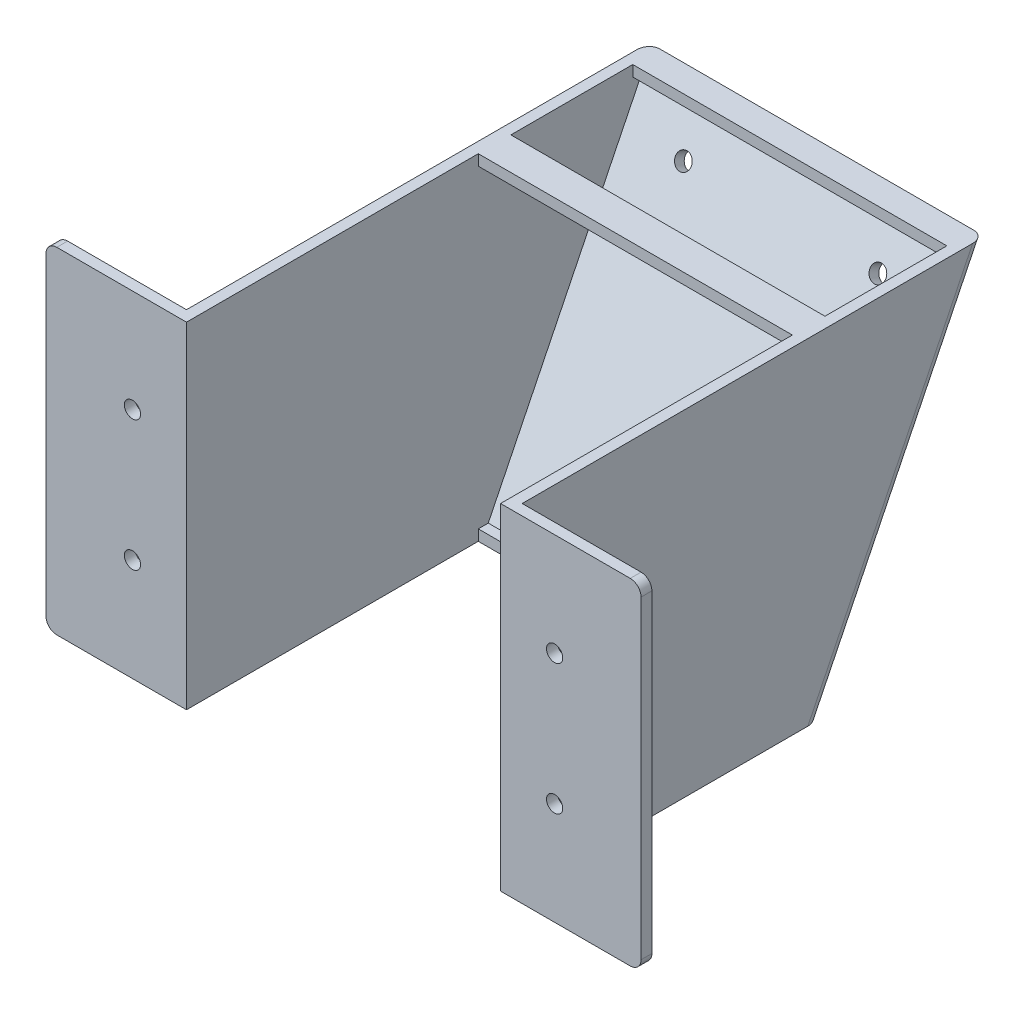
SolidWorks part; units mm, degrees
ref_plane "前视基准面" through (0, 0, 0) normal (0, 0, 1) x (1, 0, 0)
ref_plane "上视基准面" through (0, 0, 0) normal (0, 1, 0) x (1, 0, 0)
ref_plane "右视基准面" through (0, 0, 0) normal (1, 0, 0) x (0, 0, -1)
other "Configuration Table"
sketch "草图1" plane through (0, 0, 0) normal (0, 0, 1) x (1, 0, 0)
  line L5 (-31.0634, 31.0634) -> (31.0634, 31.0634)
  line L6 (-31.0634, 31.0634) -> (-31.0634, -31.0634)
  line L7 (-31.0634, -31.0634) -> (31.0634, -31.0634)
  line L8 (31.0634, 31.0634) -> (31.0634, -31.0634)
  line L9 (-31.0634, 31.0634) -> (31.0634, -31.0634) construction
  line L10 (-31.0634, -31.0634) -> (31.0634, 31.0634) construction
  point P0 (0, 0)
  point P1 (0, 0)
extrude "凸台-拉伸1" add sketch "草图1" along normal blind 57
sketch "草图3" plane through (0, 0, 57) normal (0, 0, 1) x (1, 0, 0)
  line L0 (-29.0634, 32.5965) -> (-29.0634, -33.672) construction
  line L1 (-31.0634, 31.0634) -> (-31.0634, -31.0634) construction
  line L2 (0, 32.5965) -> (0, -32.762) construction
  line L3 (29.0634, 32.5965) -> (29.0634, -33.672) construction
  line L4 (-29.0634, 31.0634) -> (29.0634, 31.0634)
  line L5 (31.0634, 31.0634) -> (-31.0634, 31.0634) construction
  line L6 (29.0634, 31.0634) -> (29.0634, -31.0634)
  line L7 (-31.0634, -31.0634) -> (31.0634, -31.0634) construction
  line L8 (29.0634, -31.0634) -> (-29.0634, -31.0634)
  line L9 (-29.0634, -31.0634) -> (-29.0634, 31.0634)
  dimension "D1" = 2
extrude "切除-拉伸5" cut sketch "草图3" against normal blind 54
sketch "草图4" plane through (31.0634, 0, 0) normal (1, 0, 0) x (0, 0, -1)
  line L0 (-55, 32.9321) -> (-55, -33.2279) construction
  line L1 (-57, -31.0634) -> (-57, 31.0634) construction
  line L2 (-57, 31.0634) -> (-55, 31.0634)
  line L3 (-57, 31.0634) -> (0, 31.0634) construction
  line L4 (-55, 31.0634) -> (-55, -31.0634)
  line L5 (-57, -31.0634) -> (0, -31.0634) construction
  line L6 (-55, -31.0634) -> (-57, -31.0634)
  line L7 (-57, -31.0634) -> (-57, 31.0634)
  dimension "D1" = 2
extrude "凸台-拉伸2" add sketch "草图4" along normal blind 24
sketch "草图5" plane through (-31.0634, 0, 0) normal (-1, 0, 0) x (0, 0, 1)
  line L0 (55, 32.4379) -> (55, -34.0321) construction
  line L1 (57, 31.0634) -> (57, -31.0634) construction
  line L2 (55, 31.0634) -> (57, 31.0634)
  line L3 (57, 31.0634) -> (0, 31.0634) construction
  line L4 (57, 31.0634) -> (57, -31.0634)
  line L5 (57, -31.0634) -> (55, -31.0634)
  line L6 (57, -31.0634) -> (0, -31.0634) construction
  line L7 (55, -31.0634) -> (55, 31.0634)
  dimension "D1" = 2
extrude "凸台-拉伸3" add sketch "草图5" along normal blind 24
sketch "草图6" plane through (0, 0, 57) normal (0, 0, 1) x (1, 0, 0)
  line L0 (39.0634, 37.283) -> (39.0634, -45.3289) construction
  line L1 (29.0634, -31.0634) -> (29.0634, 31.0634) construction
  line L2 (-58.8139, 12.0634) -> (65.5315, 12.0634) construction
  line L3 (55.0634, 31.0634) -> (29.0634, 31.0634) construction
  line L4 (0, 0) -> (0, -46.3341) construction
  line L5 (-12.2388, 0) -> (9.6324, 0) construction
  line L7 (-61.7606, -12.0634) -> (78.759, -12.0634) construction
  circle A0 centre (39.0634, 12.0634) radius 1.5
  circle A1 centre (-39.0634, 12.0634) radius 1.5
  circle A2 centre (39.0634, -12.0634) radius 1.5
  circle A3 centre (-39.0634, -12.0634) radius 1.5
  dimension "D1" = 10
  dimension "D2" = 19
extrude "切除-拉伸6" cut sketch "草图6" against normal blind 24
sketch "草图7" plane through (0, 0, 0) normal (0, 0, -1) x (-1, 0, 0)
  line L0 (0, 33.5434) -> (0, -41.5893) construction
  line L1 (-18, 33.5434) -> (-18, -43.8557) construction
  line L2 (-41.2493, 0) -> (60.1741, 0) construction
  line L3 (-41.2493, 24) -> (60.1741, 24) construction
  circle A0 centre (-18, 24) radius 1.5
  circle A1 centre (18, 24) radius 1.5
  circle A2 centre (18, -24) radius 1.5
  circle A3 centre (-18, -24) radius 1.5
  dimension "D1" = 18
  dimension "D2" = 24
extrude "切除-拉伸7" cut sketch "草图7" against normal blind 24
fillet "圆角3" radius 2 1 edges at (55.0634, -31.0634, 56)
fillet "圆角4" radius 2 1 edges at (55.0634, 31.0634, 56)
fillet "圆角5" radius 2 1 edges at (-55.0634, -31.0634, 56)
fillet "圆角6" radius 2 1 edges at (-55.0634, 31.0634, 56)
extrude "凸台-拉伸4" add sketch "草图1<2>" against normal blind 30.59
sketch "草图1<2>" plane through (0, 0, 0) normal (0, 0, 1) x (1, 0, 0) same geometry as "草图1"
sketch "草图10" plane through (0, -31.0634, 0) normal (0, -1, 0) x (1, 0, 0)
  line L0 (-29.0634, 3) -> (43.1758, 3) construction
  line L2 (-40.0027, 0) -> (49.5218, 0) construction
  dimension "D1" = 3
sketch "草图11" plane through (31.0634, 0, 0) normal (1, 0, 0) x (0, 0, -1)
  line L0 (0, 45.9565) -> (0, -37.3251) construction
  line L1 (30.59, 31.0634) -> (0, -31.2567) construction
  line L2 (30.59, 31.0634) -> (0, -31.2567)
  line L3 (0, -31.2567) -> (30.59, -31.0634)
  line L4 (30.59, -31.0634) -> (30.59, 31.0634)
extrude "切除-拉伸8" cut sketch "草图11" against normal blind 70
sketch "草图12" plane through (0, -6.0687, -12.3636) normal (0, -0.4406, -0.8977) x (-1, 0, 0)
  line L0 (-33.2875, -27.7615) -> (45.0444, -27.7615) construction
  line L1 (-33.2875, -17.7615) -> (53.4651, -17.7615) construction
  line L2 (0, 44.316) -> (0, -41.2125) construction
  line L3 (18, 44.316) -> (18, -51.7319) construction
  line L4 (-34.4065, 0) -> (38.388, 0) construction
  line L5 (-34.4065, 30.2385) -> (46.7937, 30.2385) construction
  circle A0 centre (18, -17.7615) radius 1.5
  circle A1 centre (-18, -17.7615) radius 1.5
  circle A2 centre (18, 30.2385) radius 1.5
  circle A3 centre (-18, 30.2385) radius 1.5
  dimension "D3" = 48
  dimension "D1" = 10
  dimension "D2" = 18
extrude "切除-拉伸9" cut sketch "草图12" against normal blind 10
ref_plane "基准面1" through (29.0634, 0, 0) normal (-1, 0, 0) x (0, 0, 1)
sketch "草图14" plane through (29.0634, 0, 0) normal (-1, 0, 0) x (0, 0, 1)
  line L0 (3, -29.0634) -> (3, 29.0634)
  line L1 (3, 29.0634) -> (-27.3803, 29.0634)
  line L2 (-27.3803, 29.0634) -> (1.1513, -29.0634)
  line L3 (1.1513, -29.0634) -> (3, -29.0634)
  line L7 (55, 31.0634) -> (-30.59, 31.0634) construction
  line L8 (-30.59, 31.0634) -> (-0.0949, -31.0634) construction
  line L11 (55, -31.0634) -> (-0.0949, -31.0634) construction
  line L12 (3, -31.0634) -> (3, 31.0634) construction
  point P11 (3, -29.4109)
  point P13 (3, -31.0634)
  point P14 (3.0211, -30.5087)
  point P15 (0, 0)
  dimension "D1" = 2
  dimension "D2" = 2
  dimension "D3" = 2
extrude "切除-拉伸10" cut sketch "草图14" along normal up to surface (58.1267 mm away) up to face at (-29.0634, 0, 30)
sketch "草图15" plane through (0, 31.0634, 0) normal (0, 1, 0) x (1, 0, 0)
  line L0 (-29.0634, -3) -> (-29.0634, 31.748) construction
  line L1 (29.0634, -3) -> (29.0634, 31.748) construction
  line L2 (-29.0634, -3) -> (43.1758, -3) construction
  line L3 (29.0634, 34.1697) -> (29.0634, -34.1697) construction
  line L4 (-33.5563, 25.59) -> (53.1205, 25.59) construction
  line L5 (31.0634, 30.59) -> (-31.0634, 30.59) construction
  line L6 (-29.0634, 25.59) -> (29.0634, 25.59)
  line L7 (29.0634, 25.59) -> (29.0634, 3.0302)
  line L8 (29.0634, 3.0302) -> (-29.0634, 3.0302)
  line L9 (-29.0634, 3.0302) -> (-29.0634, 25.59)
  dimension "D1" = 5
extrude "切除-拉伸11" cut sketch "草图15" against normal blind 2
fillet "圆角7" radius 2 1 edges at (-31.0634, 0, -15.3424)
fillet "圆角8" radius 2 1 edges at (31.0634, 0, -15.3424)
